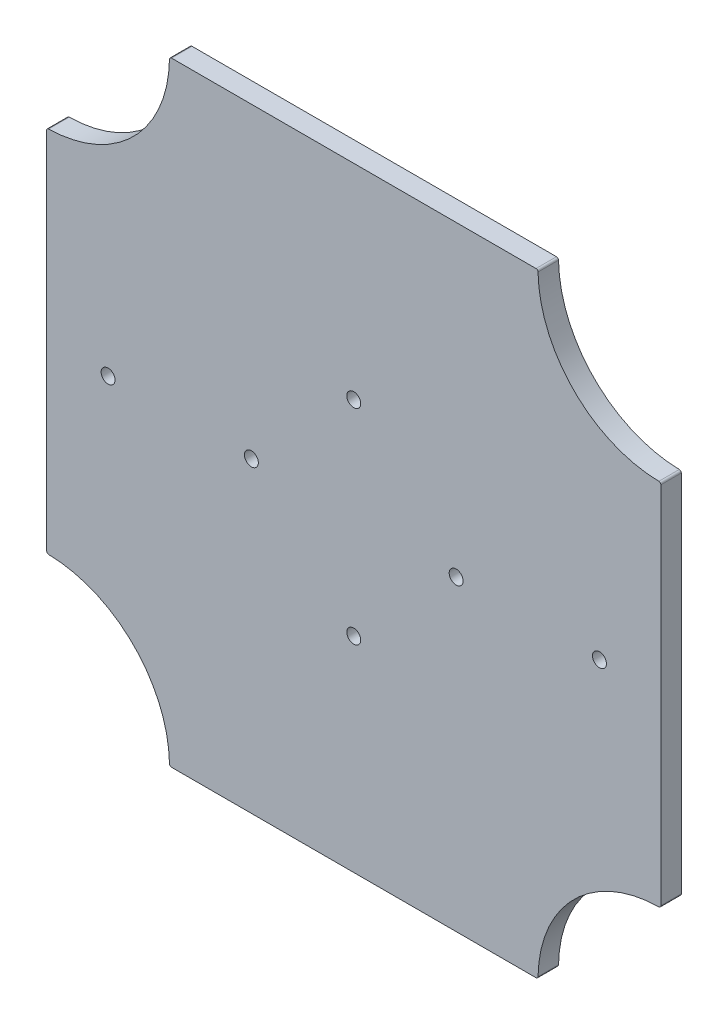
SolidWorks part; units mm, degrees
ref_plane "Plan de face" through (0, 0, 0) normal (0, 0, 1) x (1, 0, 0)
ref_plane "Plan de dessus" through (0, 0, 0) normal (0, 1, 0) x (1, 0, 0)
ref_plane "Plan de droite" through (0, 0, 0) normal (1, 0, 0) x (0, 0, -1)
sketch "Esquisse1" plane through (0, 0, 0) normal (0, 0, 1) x (1, 0, 0)
  line L0 (75, 75) -> (-75, -75) construction
  line L1 (-75, 75) -> (75, 75)
  line L2 (-75, 75) -> (-75, -75)
  line L3 (-75, -75) -> (75, -75)
  line L4 (75, 75) -> (75, -75)
  line L5 (75, -75) -> (-75, 75) construction
  dimension "D1" = 150
  dimension "D2" = 150
extrude "Boss.-Extru.1" add sketch "Esquisse1" along normal blind 5
sketch "Esquisse2" plane through (0, 0, 5) normal (0, 0, 1) x (1, 0, 0)
  line L0 (75, 75) -> (-75, 75) construction
  line L1 (75, -75) -> (75, 75) construction
  line L2 (45, 75) -> (75, 75)
  line L3 (75, 75) -> (75, 45)
  line L4 (75, -75) -> (45, -75)
  line L5 (75, -45) -> (75, -75)
  line L6 (-75, -75) -> (-75, -45)
  line L7 (-45, -75) -> (-75, -75)
  line L8 (-75, 75) -> (-45, 75)
  line L9 (-75, 45) -> (-75, 75)
  arc A0 (45, 75) -> (75, 45) centre (75, 75) ccw
  arc A1 (75, -45) -> (45, -75) centre (75, -75) ccw
  arc A2 (-45, -75) -> (-75, -45) centre (-75, -75) ccw
  arc A3 (-75, 45) -> (-45, 75) centre (-75, 75) ccw
  point P20 (0, 0)
  point P21 (0, 0)
  dimension "D1" = 30
  dimension "D2" = 4
extrude "Enlèv. mat.-Extru.1" cut sketch "Esquisse2" against normal up to surface (5 mm away) up to face at (0, 0, 0)
hole_wizard "Dégagement M31" positions "Esquisse3" profile "Esquisse4" hole size "M3" standard "ISO" end condition up to next
sketch "Esquisse3" plane through (0, 0, 0) normal (0, 0, -1) x (-1, 0, 0)
  line L0 (-75, -45) -> (-75, 45) construction
  line L1 (75, 45) -> (75, -45) construction
  point P0 (0, 25)
  point P2 (0, -25)
  point P4 (60, 0)
  point P6 (25, 0)
  point P8 (-25, 0)
  point P10 (-60, 0)
  dimension "D1" = 25
  dimension "D2" = 25
  dimension "D3" = 25
  dimension "D4" = 25
  dimension "D5" = 15
  dimension "D6" = 15
sketch "Esquisse4" plane through (0, 25, 0) normal (1, 0, 0) x (0, 1, 0)
  line L0 (0, 0) -> (0, 5)
  line L1 (0, 5) -> (1.7, 5)
  line L2 (1.7, 5) -> (1.7, 0)
  line L5 (1.7, 0) -> (0, 0)
  line L11 (0, -6.35) -> (0, 107.95) construction
  dimension "Diamètre du perçage jusqu'au prochain" = 3.4
  dimension "Profondeur du perçage jusqu'au prochain" = 5
fillet "Congé1" radius 0.5 8 edges at (75, 45, 2.5) (45, 75, 2.5) (-45, 75, 2.5) (-75, 45, 2.5) (-75, -45, 2.5) (-45, -75, 2.5) (75, -45, 2.5) (45, -75, 2.5)
